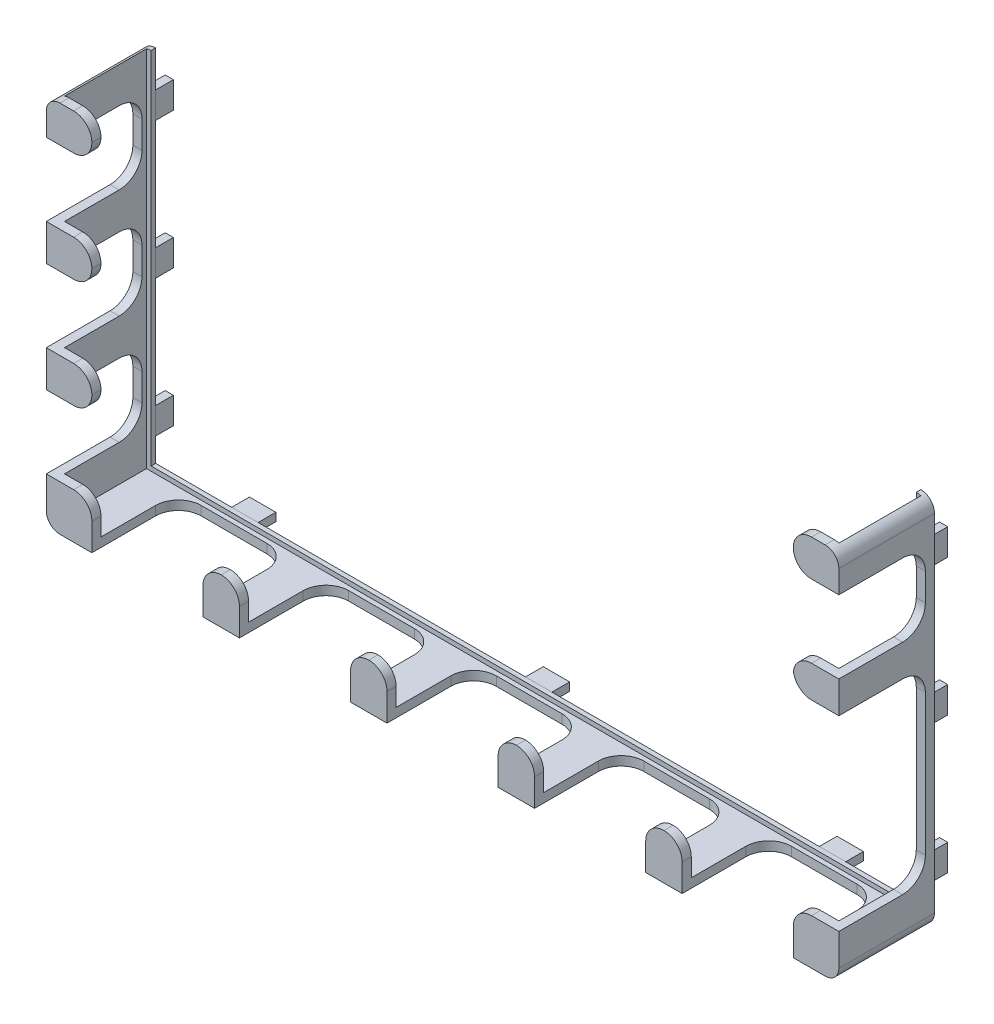
SolidWorks part; units mm, degrees
ref_plane "Front Plane" through (0, 0, 0) normal (0, 0, 1) x (1, 0, 0)
ref_plane "Top Plane" through (0, 0, 0) normal (0, 1, 0) x (1, 0, 0)
ref_plane "Right Plane" through (0, 0, 0) normal (1, 0, 0) x (0, 0, -1)
sketch "Sketch9" plane through (0, 0, 0) normal (0, 0, -1) x (1, 0, 0)
  line L1 (-85.9, 32.9) -> (-84.1, 32.9)
  line L2 (-85.9, 32.9) -> (-85.9, 27.1)
  line L3 (-85.9, 27.1) -> (-84.1, 27.1)
  line L4 (-84.1, 32.9) -> (-84.1, 27.1)
  line L5 (-85.9, 2.9) -> (-84.1, 2.9)
  line L6 (-85.9, 2.9) -> (-85.9, -2.9)
  line L7 (-85.9, -2.9) -> (-84.1, -2.9)
  line L8 (-84.1, 2.9) -> (-84.1, -2.9)
  line L9 (-85.9, -27.1) -> (-84.1, -27.1)
  line L10 (-85.9, -27.1) -> (-85.9, -32.9)
  line L11 (-85.9, -32.9) -> (-84.1, -32.9)
  line L12 (-84.1, -27.1) -> (-84.1, -32.9)
  line L13 (84.1, 32.9) -> (85.9, 32.9)
  line L14 (84.1, 32.9) -> (84.1, 27.1)
  line L15 (84.1, 27.1) -> (85.9, 27.1)
  line L16 (85.9, 32.9) -> (85.9, 27.1)
  line L21 (84.1, -27.1) -> (85.9, -27.1)
  line L22 (84.1, -27.1) -> (84.1, -32.9)
  line L23 (84.1, -32.9) -> (85.9, -32.9)
  line L24 (85.9, -27.1) -> (85.9, -32.9)
  line L27 (84.1, 2.9) -> (85.9, 2.9)
  line L28 (84.1, 2.9) -> (84.1, -2.9)
  line L29 (84.1, -2.9) -> (85.9, -2.9)
  line L30 (85.9, 2.9) -> (85.9, -2.9)
  line L33 (-67.4, 39.9) -> (-61.6, 39.9)
  line L34 (-67.4, 39.9) -> (-67.4, 38.1)
  line L35 (-67.4, 38.1) -> (-61.6, 38.1)
  line L36 (-61.6, 39.9) -> (-61.6, 38.1)
  line L37 (-2.9, 39.9) -> (2.9, 39.9)
  line L38 (-2.9, 39.9) -> (-2.9, 38.1)
  line L39 (-2.9, 38.1) -> (2.9, 38.1)
  line L40 (2.9, 39.9) -> (2.9, 38.1)
  line L41 (61.6, 39.9) -> (67.4, 39.9)
  line L42 (61.6, 39.9) -> (61.6, 38.1)
  line L43 (61.6, 38.1) -> (67.4, 38.1)
  line L44 (67.4, 39.9) -> (67.4, 38.1)
  point P16 (0, 38.1)
  point P18 (85.9, 0)
  point P19 (-67.4, 39)
  point P24 (-85.9, 30)
  point P25 (-85.9, -30)
  point P26 (-64.5, 39.9)
  point P27 (64.5, 39.9)
  point P28 (85, 32.9)
  point P29 (-85, -32.9)
  point P30 (-84.1, 0)
  dimension "D1" = 5.8
  dimension "D2" = 1.8
  dimension "D3" = 9
  dimension "D4" = 85
  dimension "D5" = 30
  dimension "D6" = 30
  dimension "D7" = 64.5
  dimension "D8" = 64.5
  dimension "D9" = 85
extrude "Boss-Extrude8" add sketch "Sketch9" along normal blind 4
sketch "Sketch1" plane through (0, 0, 0) normal (0, 0, 1) x (1, 0, 0)
  line L1 (-87, -41) -> (87, -41) construction
  line L2 (-87, -41) -> (-87, 41) construction
  line L3 (-87, 41) -> (87, 41) construction
  line L4 (87, -41) -> (87, 41) construction
  line L5 (-87, -41) -> (87, 41) construction
  line L6 (-87, 41) -> (87, -41) construction
  line L7 (-87, 41) -> (-85, 41)
  line L8 (-87, 41) -> (-87, -41)
  line L10 (-85, 41) -> (-85, -39)
  line L11 (-87, -41) -> (87, -41)
  line L13 (-85, -39) -> (85, -39)
  line L15 (87, 41) -> (85, 41)
  line L16 (87, 41) -> (87, -41)
  line L18 (85, 41) -> (85, -39)
  point P0 (0, 0)
  dimension "D1" = 174
  dimension "D2" = 82
  dimension "D3" = 2
  dimension "D4" = 2
extrude "Boss-Extrude5" add sketch "Sketch1" along normal blind 19
sketch "Sketch7" plane through (0, 0, 19) normal (0, 0, 1) x (1, 0, 0)
  line L0 (-87, -41) -> (87, -41) construction
  line L1 (-87, 41) -> (-77, 41)
  line L2 (-87, 41) -> (-87, -41)
  line L4 (-77, 41) -> (-77, -31)
  line L9 (-77, -31) -> (77, -31)
  line L11 (-87, -41) -> (87, -41)
  line L19 (77, -31) -> (77, 41)
  line L20 (77, 41) -> (87, 41)
  line L21 (87, -41) -> (87, 41)
  line L22 (-87, 41) -> (-87, -41) construction
  dimension "D1" = 10
  dimension "D2" = 10
  dimension "D3" = 10
extrude "Boss-Extrude6" add sketch "Sketch7" along normal blind 2
sketch "Sketch17" plane through (0, 0, 0) normal (0, 0, 1) x (1, 0, 0)
  line L0 (-84, 41) -> (-85, 41)
  line L1 (85, 41) -> (84, 41)
  line L2 (85, 41) -> (85, -39)
  line L3 (85, -39) -> (-85, -39)
  line L4 (-85, 41) -> (-85, -39)
  line L6 (-84, 41) -> (-84, -38)
  line L7 (-84, -38) -> (84, -38)
  line L8 (84, 41) -> (84, -38)
  dimension "D1" = 1
  dimension "D2" = 1
extrude "Boss-Extrude11" add sketch "Sketch17" along normal blind 1
sketch "Sketch18" plane through (0, 0, 0) normal (-1, 0, 0) x (0, 0, 1)
  line L0 (21, 41) -> (21, -41) construction
  line L1 (2, 33) -> (21, 33)
  line L2 (2, 33) -> (2, 17)
  line L3 (2, 17) -> (21, 17)
  line L4 (21, 33) -> (21, 17)
  line L5 (2, 9) -> (21, 9)
  line L6 (2, 9) -> (2, -7)
  line L7 (2, -7) -> (21, -7)
  line L8 (21, 9) -> (21, -7)
  line L9 (2, -15) -> (21, -15)
  line L10 (2, -15) -> (2, -31)
  line L11 (2, -31) -> (21, -31)
  line L12 (21, -15) -> (21, -31)
  line L13 (1, -38) -> (1, 41) construction
  line L18 (21, 41) -> (19, 41) construction
  line L19 (19, -39) -> (1, -39) construction
  dimension "D1" = 1
  dimension "D2" = 8
  dimension "D3" = 8
  dimension "D4" = 8
  dimension "D5" = 8
extrude "Cut-Extrude6" cut sketch "Sketch18" against normal through all both and the other way through all
sketch "Sketch19" plane through (0, 0, 0) normal (0, -1, 0) x (1, 0, 0)
  line L1 (-77, 2) -> (-52.6, 2)
  line L2 (-77, 2) -> (-77, 21)
  line L3 (-77, 21) -> (-52.6, 21)
  line L4 (-52.6, 2) -> (-52.6, 21)
  line L5 (-44.6, 2) -> (-20.2, 2)
  line L6 (-44.6, 2) -> (-44.6, 21)
  line L7 (-44.6, 21) -> (-20.2, 21)
  line L8 (-20.2, 2) -> (-20.2, 21)
  line L9 (-12.2, 2) -> (12.2, 2)
  line L10 (-12.2, 2) -> (-12.2, 21)
  line L11 (-12.2, 21) -> (12.2, 21)
  line L12 (12.2, 2) -> (12.2, 21)
  line L13 (20.2, 2) -> (44.6, 2)
  line L14 (20.2, 2) -> (20.2, 21)
  line L15 (20.2, 21) -> (44.6, 21)
  line L16 (44.6, 2) -> (44.6, 21)
  line L17 (52.6, 2) -> (77, 2)
  line L18 (52.6, 2) -> (52.6, 21)
  line L19 (52.6, 21) -> (77, 21)
  line L20 (77, 2) -> (77, 21)
  line L23 (77, 2) -> (85, 2) construction
  line L24 (52.6, 2) -> (44.6, 2) construction
  line L25 (20.2, 2) -> (12.2, 2) construction
  line L26 (-12.2, 2) -> (-20.2, 2) construction
  line L27 (-44.6, 2) -> (-52.6, 2) construction
  line L28 (-77, 2) -> (-85, 2) construction
  line L29 (87, 21) -> (-87, 21) construction
  line L31 (84, 1) -> (-84, 1) construction
  line L32 (-85, 19) -> (-85, 2) construction
  line L33 (85, 2) -> (85, 19) construction
  dimension "D1" = 8
  dimension "D2" = 1
extrude "Cut-Extrude8" cut sketch "Sketch19" along normal through all
sketch "Sketch10" plane through (0, 0, 21) normal (0, 0, 1) x (1, 0, 0)
  line L0 (77, 41) -> (77, 33) construction
  line L1 (77, 10) -> (87, 10)
  line L2 (77, 10) -> (77, -24)
  line L3 (77, -24) -> (87, -24)
  line L4 (87, 10) -> (87, -24)
  line L5 (87, -41) -> (87, -31) construction
  dimension "D1" = 24
  dimension "D2" = 10
extrude "Cut-Extrude9" cut sketch "Sketch10" against normal up to vertex (19 mm away) up to point (87, 9, 2)
fillet "Fillet3" radius 4 20 edges at (-77, 41, 20) (-77, 33, 20) (-77, 17, 20) (-77, 9, 20) (-77, -7, 20) (-77, -15, 20) (-77, -31, 20) (-52.6, -31, 20) (-44.6, -31, 20) (44.6, -31, 20) (12.2, -31, 20) (-20.2, -31, 20) (-12.2, -31, 20) (20.2, -31, 20) (52.6, -31, 20) (77, -31, 20) (77, 17, 20) (77, 10, 20) (77, 33, 20) (77, 41, 20)
fillet "Fillet4" radius 5 20 edges at (86, 33, 2) (86, 17, 2) (86, 10, 2) (86, -31, 2) (77, -40, 2) (52.6, -40, 2) (44.6, -40, 2) (12.2, -40, 2) (20.2, -40, 2) (-20.2, -40, 2) (-12.2, -40, 2) (-44.6, -40, 2) (-52.6, -40, 2) (-77, -40, 2) (-86, 9, 2) (-86, -15, 2) (-86, -31, 2) (-86, -7, 2) (-86, 17, 2) (-86, 33, 2)
fillet "Fillet5" radius 3 4 edges at (-87, 41, 10.5) (-87, -41, 10.5) (87, -41, 10.5) (87, 41, 10.5)
sketch "Sketch20" plane through (87, 0, 0) normal (1, 0, 0) x (0, 0, -1)
  line L1 (-3.9004, 35.1743) -> (9.2506, 35.1743)
  line L2 (-3.9004, 35.1743) -> (-3.9004, 24.0332)
  line L3 (-3.9004, 24.0332) -> (9.2506, 24.0332)
  line L4 (9.2506, 35.1743) -> (9.2506, 24.0332)
  line L5 (-3.9004, 35.1743) -> (9.2506, 24.0332) construction
  line L6 (-3.9004, 24.0332) -> (9.2506, 35.1743) construction
  point P0 (2.6751, 29.6037)
extrude "Boss-Extrude12" [suppressed] add sketch "Sketch20" against normal blind 10 separate body
other "Intersect1" [suppressed]
equation "\"D4@Sketch1\"=\"D3@Sketch1\""
equation "\"D2@Sketch17\"=\"D1@Sketch17\""
